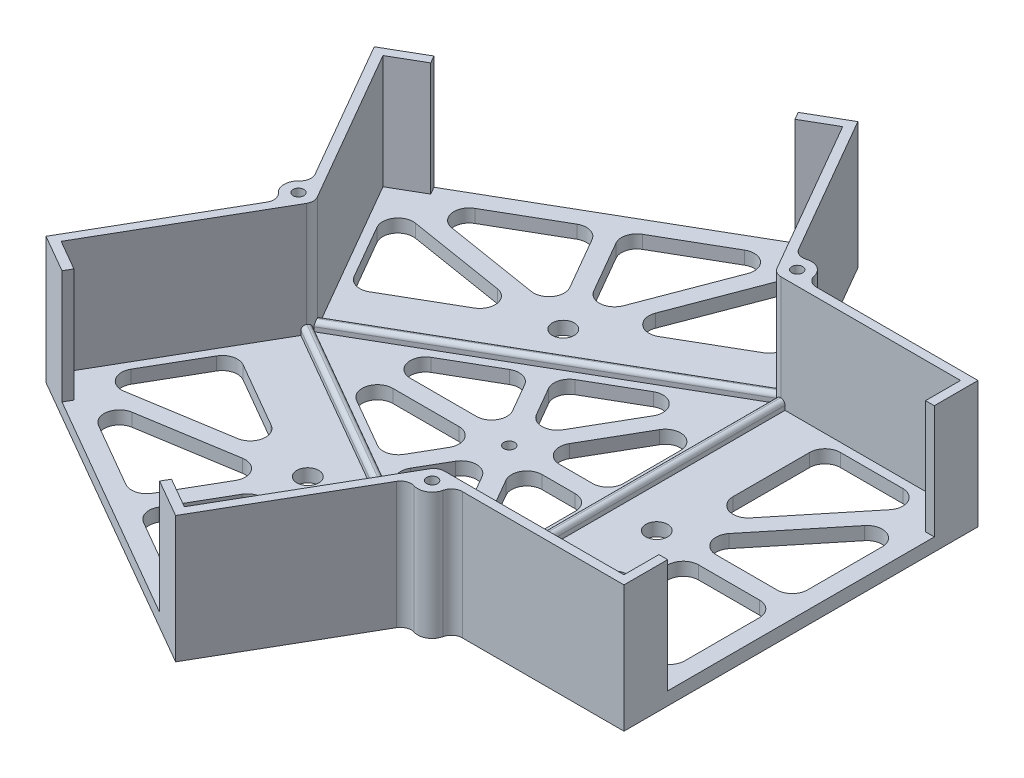
SolidWorks part; units mm, degrees
ref_plane "Front Plane" through (0, 0, 0) normal (0, 0, 1) x (1, 0, 0)
ref_plane "Top Plane" through (0, 0, 0) normal (0, 1, 0) x (1, 0, 0)
ref_plane "Right Plane" through (0, 0, 0) normal (1, 0, 0) x (0, 0, -1)
sketch "Sketch1" plane through (0, 0, 0) normal (0, 1, 0) x (1, 0, 0)
  line L0 (-19.4617, -68.9294) -> (-33.415, -32.2478)
  line L1 (-15.5479, 2.6989) -> (-16.7979, 0.5338)
  line L2 (50.5658, -38.8837) -> (50.5658, 42.1163)
  line L3 (-49.5423, -56.1811) -> (-14.4683, -76.4311)
  line L4 (-66.1729, -6.1649) -> (-66.1729, -0.3837)
  line L5 (-49.5423, -56.1811) -> (-84.6163, -35.9311)
  line L6 (-84.6163, -35.9311) -> (-68.1729, -7.4503)
  line L7 (-84.6163, 39.1637) -> (-68.1729, 10.683)
  line L8 (-14.4683, 79.6637) -> (1.9751, 51.183)
  line L9 (-66.1729, 1.6163) -> (-18.4823, 1.6163)
  line L10 (-84.6163, 39.1637) -> (-14.4683, 79.6637)
  line L11 (50.5658, 42.1163) -> (17.679, 42.1163)
  line L12 (50.5658, -38.8837) -> (17.679, -38.8837)
  line L13 (-14.4683, -76.4311) -> (1.9751, -47.9503)
  line L14 (2.0883, 48.8082) -> (7.095, 45.9176)
  line L15 (-33.7744, -24.8702) -> (-66.1729, -6.1649)
  line L16 (8.8271, 44.9176) -> (-15.0182, 3.6163)
  line L17 (-68.1729, -7.4503) -> (-68.1729, 10.683)
  line L18 (-38.91, -26.5239) -> (-65.6522, -11.0843)
  line L19 (19.5658, -4.0044) -> (19.5658, -34.8837)
  line L20 (1.9751, -47.9503) -> (17.679, -38.8837)
  line L21 (1.9751, 51.183) -> (17.679, 42.1163)
  line L22 (15.5658, -0.3837) -> (15.5658, -37.7943)
  line L23 (-29.1746, 35.3773) -> (-2.4324, 50.817)
  line L24 (10.5591, 43.9176) -> (15.5658, 41.027)
  line L25 (15.5658, -37.7943) -> (10.5591, -40.6849)
  line L26 (-30.3103, 30.1029) -> (2.0883, 48.8082)
  line L27 (8.8271, -41.6849) -> (-15.0182, -0.3837)
  line L28 (-17.3276, 3.6163) -> (-31.7524, 28.6007)
  line L29 (-17.4229, 1.6163) -> (-14.9229, 1.6163)
  line L30 (-17.3276, -0.3837) -> (-31.7524, -25.368)
  line L31 (-15.5479, 0.5338) -> (-16.7979, 2.6989)
  line L32 (-65.6522, 14.317) -> (-38.91, 29.7566)
  line L33 (19.5658, 38.1163) -> (19.5658, 7.2371)
  line L34 (-2.4324, -47.5843) -> (-29.1746, -32.1447)
  line L35 (-66.1729, 9.3975) -> (-33.7744, 28.1029)
  line L36 (15.5658, 41.027) -> (15.5658, 3.6163)
  line L37 (2.0883, -45.5755) -> (-30.3103, -26.8702)
  line L38 (7.095, 45.9176) -> (-16.1729, 5.6163)
  line L39 (-66.1729, -0.3837) -> (-19.637, -0.3837)
  line L40 (10.5591, -40.6849) -> (-12.7088, -0.3837)
  line L41 (10.5591, 43.9176) -> (-12.7088, 3.6163)
  line L42 (-66.1729, 3.6163) -> (-19.637, 3.6163)
  line L43 (7.095, -42.6849) -> (-16.1729, -2.3837)
  line L44 (-13.8635, 1.6163) -> (14.9859, 1.6163)
  line L45 (-16.1729, 5.6163) -> (-30.3103, 30.1029)
  line L46 (-12.7088, 3.6163) -> (15.5658, 3.6163)
  line L47 (-19.637, -0.3837) -> (-33.7744, -24.8702)
  line L48 (-19.637, 3.6163) -> (-33.7744, 28.1029)
  line L49 (-12.7088, -0.3837) -> (15.5658, -0.3837)
  line L50 (-16.1729, -2.3837) -> (-30.3103, -26.8702)
  line L51 (-53.8858, -0.3837) -> (-28.1992, -15.2138)
  line L52 (4.4155, -30.0439) -> (4.4155, -0.3837)
  line L53 (0.9514, 35.2766) -> (-24.7351, 20.4465)
  line L54 (4.4155, 3.6163) -> (4.4155, 33.2766)
  line L55 (-78.2327, 36.1069) -> (-65.6522, 14.317)
  line L56 (-75.6229, 39.7373) -> (-49.2744, 54.9496)
  line L57 (-15.0128, 72.6069) -> (-2.4324, 50.817)
  line L58 (-15.0128, -69.3743) -> (-2.4324, -47.5843)
  line L59 (-45.8103, -53.717) -> (-19.4617, -68.9294)
  line L60 (-49.2744, -51.717) -> (-75.6229, -36.5046)
  line L61 (-78.2327, -32.8743) -> (-65.6522, -11.0843)
  line L62 (44.7266, 38.1163) -> (19.5658, 38.1163)
  line L63 (-28.1992, 18.4465) -> (-53.8858, 3.6163)
  line L64 (46.5658, -30.8084) -> (46.5658, -0.3837)
  line L65 (44.7266, -34.8837) -> (19.5658, -34.8837)
  line L66 (-24.7351, -17.2138) -> (0.9514, -32.0439)
  line L67 (-38.91, -26.5239) -> (-78.2327, -32.8743)
  line L68 (-15.0128, -69.3743) -> (-29.1746, -32.1447)
  line L69 (-66.1729, 3.6163) -> (-66.1729, 9.3975)
  line L70 (44.7266, 38.1163) -> (19.5658, 7.2371)
  line L71 (7.095, -42.6849) -> (2.0883, -45.5755)
  line L72 (-29.1746, 35.3773) -> (-15.0128, 72.6069)
  line L73 (-78.2327, 36.1069) -> (-38.91, 29.7566)
  line L74 (-36.8791, -30.2478) -> (-75.6229, -36.5046)
  line L75 (46.5658, 34.041) -> (21.7753, 3.6163)
  line L76 (21.7753, -0.3837) -> (46.5658, -30.8084)
  line L77 (-33.415, 35.4804) -> (-19.4617, 72.162)
  line L78 (-75.6229, 39.7373) -> (-36.8791, 33.4804)
  line L79 (46.5658, 3.6163) -> (46.5658, 34.041)
  line L80 (19.5658, -4.0044) -> (44.7266, -34.8837)
  line L81 (-45.8103, 56.9496) -> (-19.4617, 72.162)
  line L82 (46.5658, 3.6163) -> (21.7753, 3.6163)
  line L83 (-33.415, 35.4804) -> (-45.8103, 56.9496)
  line L84 (-45.8103, -53.717) -> (-33.415, -32.2478)
  line L85 (46.5658, -0.3837) -> (21.7753, -0.3837)
  line L86 (-36.8791, 33.4804) -> (-49.2744, 54.9496)
  line L87 (-49.2744, -51.717) -> (-36.8791, -30.2478)
  circle A0 centre (-33.0423, -27.6023) radius 2.5
  circle A1 centre (-33.0423, 30.8349) radius 2.5
  circle A2 centre (17.5658, 1.6163) radius 2.5
  circle A3 centre (-16.1729, 1.6163) radius 1.25
  point P6 (50.5658, 1.6163)
  point P11 (-49.5423, -56.1811)
  point P14 (-49.5423, 59.4137)
  point P15 (-49.5423, -56.1811)
  point P26 (-68.1729, 1.6163)
  point P32 (9.8271, -43.417)
  point P36 (9.8271, 46.6496)
  point P64 (-16.1729, 1.6163)
  point P94 (-16.1729, 1.6163)
extrude "Boss-Extrude1" add sketch "Sketch1" along normal blind 3 contours L21 L8 L10 L7 L17 L6 L5 L3 L13 L20 L12 L2 L11 A3 A2 A1 A0 L87 L60 L74 L86 L78 | L69 L42 L63 L48 L35 | L53 L38 L14 L26 L45 | L54 L46 L36 L24 L41 | L52 L40 L25 L22 L49 | L71 L43 L66 L50 L37 | L51 L39 L4 L15 L47 region at (34.1224, 0, 36.8187) region at (-47.1024, 0, 10.9831) region at (-11.6196, 0, -34.7018) region at (10.2032, 0, 18.8697) region at (10.2032, 0, -22.1024) region at (-47.1024, 0, -14.2157) region at (-11.6196, 0, 31.4691)
sketch "Sketch2" plane through (0, 3, 0) normal (0, 1, 0) x (1, 0, 0)
  line L1 (-14.4683, 79.6637) -> (1.9751, 51.183)
  line L2 (1.9751, 51.183) -> (17.679, 42.1163)
  line L3 (17.679, 42.1163) -> (50.5658, 42.1163)
  line L5 (50.5658, -38.8837) -> (17.679, -38.8837)
  line L6 (17.679, -38.8837) -> (1.9751, -47.9503)
  line L7 (1.9751, -47.9503) -> (-14.4683, -76.4311)
  line L9 (-84.6163, -35.9311) -> (-68.1729, -7.4503)
  line L10 (-68.1729, -7.4503) -> (-68.1729, 10.683)
  line L11 (-68.1729, 10.683) -> (-84.6163, 39.1637)
  line L12 (-60.6289, 1.6163) -> (-62.9383, 1.6163)
  line L13 (6.055, 40.1163) -> (7.2097, 42.1163)
  line L14 (9.8271, -43.417) -> (7.316, -39.0678)
  line L15 (-60.6289, 1.6163) -> (-81.8843, 38.4317)
  line L17 (-15.2003, 76.9317) -> (6.055, 40.1163)
  line L18 (6.055, 40.1163) -> (48.5658, 40.1163)
  line L20 (48.5658, -36.8837) -> (6.055, -36.8837)
  line L21 (6.055, -36.8837) -> (-15.2003, -73.699)
  line L23 (-81.8843, -35.199) -> (-60.6289, 1.6163)
  line L24 (-15.2003, -73.699) -> (-81.8843, -35.199) construction
  line L25 (-14.4683, -76.4311) -> (-84.6163, -35.9311) construction
  line L26 (-81.8843, -35.199) -> (-74.9561, -39.199)
  line L27 (-74.9561, -39.199) -> (-75.9561, -40.9311)
  line L28 (-14.4683, -76.4311) -> (-84.6163, -35.9311) construction
  line L29 (-75.9561, -40.9311) -> (-84.6163, -35.9311)
  line L30 (-15.2003, -73.699) -> (-22.1285, -69.699)
  line L31 (-22.1285, -69.699) -> (-23.1285, -71.4311)
  line L32 (-23.1285, -71.4311) -> (-14.4683, -76.4311)
  line L33 (48.5658, 40.1163) -> (48.5658, 32.1163)
  line L34 (48.5658, 40.1163) -> (48.5658, -36.8837) construction
  line L35 (50.5658, 42.1163) -> (50.5658, -38.8837) construction
  line L36 (-84.6163, 39.1637) -> (-14.4683, 79.6637) construction
  line L37 (-81.8843, 38.4317) -> (-15.2003, 76.9317) construction
  line L38 (48.5658, 32.1163) -> (50.5658, 32.1163)
  line L39 (50.5658, -38.8837) -> (50.5658, 42.1163) construction
  line L40 (50.5658, 32.1163) -> (50.5658, 42.1163)
  line L41 (48.5658, -36.8837) -> (48.5658, -28.8837)
  line L42 (48.5658, -28.8837) -> (50.5658, -28.8837)
  line L43 (50.5658, -28.8837) -> (50.5658, -38.8837)
  line L44 (-15.2003, 76.9317) -> (-22.1285, 72.9317)
  line L45 (-22.1285, 72.9317) -> (-23.1285, 74.6637)
  line L46 (-84.6163, 39.1637) -> (-14.4683, 79.6637) construction
  line L47 (-23.1285, 74.6637) -> (-14.4683, 79.6637)
  line L48 (-81.8843, 38.4317) -> (-74.9561, 42.4317)
  line L49 (-74.9561, 42.4317) -> (-75.9561, 44.1637)
  line L50 (-75.9561, 44.1637) -> (-84.6163, 39.1637)
  line L51 (-84.6163, -35.9311) -> (-62.9383, 1.6163) construction
  line L52 (-63.1509, 1.6163) -> (-68.1729, 1.6163)
  line L53 (-62.9383, 1.6163) -> (-84.6163, 39.1637) construction
  line L54 (7.2097, -38.8837) -> (-14.4683, -76.4311) construction
  line L55 (7.2097, -38.8837) -> (6.055, -36.8837)
  line L56 (50.5658, -38.8837) -> (7.2097, -38.8837) construction
  line L57 (7.2097, 42.1163) -> (50.5658, 42.1163) construction
  line L58 (7.316, 42.3005) -> (9.8271, 46.6496)
  line L59 (-14.4683, 79.6637) -> (7.2097, 42.1163) construction
  circle A3 centre (-64.4009, 1.6163) radius 1.25
  circle A4 centre (7.941, -40.1503) radius 1.25
  circle A5 centre (7.941, 43.383) radius 1.25
  dimension "D1" = 2
extrude "Boss-Extrude2" add sketch "Sketch2" along normal blind 26 contours L49 L50 L11 L9 L29 L27 L26 L23 L15 L48 | A3 L10 L9 | A3 L11 L10 | L47 L45 L44 L17 L18 L33 L38 L40 L3 L1 | A5 L3 L2 | A5 L2 L1 | L43 L42 L41 L20 L21 L30 L31 L32 L7 L5 | A4 L7 L6 | A4 L6 L5 region at (-7.0061, 3, -64.9848) region at (34.1224, 3, 38.0067) region at (-75.629, 3, 22.1328)
sketch "Sketch3" plane through (0, 29, 0) normal (0, 1, 0) x (1, 0, 0)
  line L0 (-84.6163, 39.1637) -> (-64.8095, 4.8573)
  line L1 (-84.6163, -35.9311) -> (-64.8095, -1.6247)
  line L2 (-14.4683, -76.4311) -> (5.3385, -42.1247)
  line L3 (50.5658, -38.8837) -> (10.9521, -38.8837)
  line L4 (50.5658, 42.1163) -> (10.9521, 42.1163)
  line L6 (-14.4683, 79.6637) -> (5.3385, 45.3573)
  line L7 (1.9751, 51.183) -> (17.679, 42.1163)
  line L8 (-68.1729, -7.4503) -> (-68.1729, 10.683)
  line L9 (17.679, -38.8837) -> (1.9751, -47.9503)
  circle A0 centre (-64.4009, 1.6163) radius 3.2667
  circle A1 centre (7.941, 43.383) radius 3.2667
  circle A2 centre (7.941, -40.1503) radius 3.2667
  line M4 (-68.1729, 10.683) -> (-68.1729, -7.4503)
extrude "Cut-Extrude1" cut sketch "Sketch3" against normal through all contours A0 L0 L1 M4 | A2 L2 L9 L3 | A1 L4 L7 L6 region at (-66.6509, 29, -7.6779) region at (3.8139, 29, 45.1282) region at (14.3156, 29, -42.2977)
fillet "Fillet1" radius 2.5 9 edges at (6.055, 16, 36.8837) (-60.6289, 16, -1.6163) (6.055, 16, -40.1163) (5.3385, 14.5, -45.3573) (10.9521, 14.5, -42.1163) (5.3385, 14.5, 42.1247) (10.9521, 14.5, 38.8837) (-64.8095, 14.5, 1.6247) (-64.8095, 14.5, -4.8573)
fillet "Fillet2" radius 3.5 54 edges at (-33.415, 1.5, -35.4804) (-2.4324, 1.5, -50.817) (-19.4617, 1.5, -72.162) (-15.0128, 1.5, -72.6069) (-29.1746, 1.5, -35.3773) (-75.6229, 1.5, -39.7373) (-78.2327, 1.5, -36.1069) (-65.6522, 1.5, -14.317) (-38.91, 1.5, -29.7566) (-36.8791, 1.5, -33.4804) (-49.2744, 1.5, -54.9496) (-45.8103, 1.5, -56.9496) (46.5658, 1.5, -34.041) (44.7266, 1.5, -38.1163) (19.5658, 1.5, -38.1163) (46.5658, 1.5, 30.8084) (44.7266, 1.5, 34.8837) (19.5658, 1.5, 34.8837) (46.5658, 1.5, 0.3837) (46.5658, 1.5, -3.6163) (19.5658, 1.5, -7.2371) (21.7753, 1.5, -3.6163) (19.5658, 1.5, 4.0044) (21.7753, 1.5, 0.3837) (0.9514, 1.5, 32.0439) (4.4155, 1.5, 30.0439) (4.4155, 1.5, 0.3837) (4.4155, 1.5, -3.6163) (4.4155, 1.5, -33.2766) (0.9514, 1.5, -35.2766) (-24.7351, 1.5, -20.4465) (-12.7088, 1.5, 0.3837) (-16.1729, 1.5, 2.3837) (-16.1729, 1.5, -5.6163) (-12.7088, 1.5, -3.6163) (-28.1992, 1.5, -18.4465) (-19.637, 1.5, -3.6163) (-19.637, 1.5, 0.3837) (-28.1992, 1.5, 15.2138) (-24.7351, 1.5, 17.2138) (-53.8858, 1.5, -3.6163) (-53.8858, 1.5, 0.3837) (-2.4324, 1.5, 47.5843) (-19.4617, 1.5, 68.9294) (-15.0128, 1.5, 69.3743) (-29.1746, 1.5, 32.1447) (-33.415, 1.5, 32.2478) (-36.8791, 1.5, 30.2478) (-38.91, 1.5, 26.5239) (-45.8103, 1.5, 53.717) (-49.2744, 1.5, 51.717) (-65.6522, 1.5, 11.0843) (-75.6229, 1.5, 36.5046) (-78.2327, 1.5, 32.8743)
sketch "Sketch4" plane through (0, 3, 0) normal (0, 1, 0) x (1, 0, 0)
  line L0 (-57.3499, 1.6163) -> (4.4155, 37.2766)
  line L1 (-61.3499, 1.6163) -> (6.4155, 40.7407)
  line L2 (4.4155, -34.0439) -> (4.4155, 37.2766)
  line L3 (-57.3499, 1.6163) -> (4.4155, -34.0439)
  line L4 (6.4155, -37.508) -> (6.4155, 40.7407)
  line L5 (-61.3499, 1.6163) -> (6.4155, -37.508)
  line L6 (-65.3499, 1.6163) -> (8.4155, 44.2048)
  line L7 (8.4155, -40.9721) -> (8.4155, 44.2048)
  line L8 (-65.3499, 1.6163) -> (8.4155, -40.9721)
  circle A0 centre (-63.5157, 1.6163) radius 2.5
  circle A1 centre (7.4984, 42.6163) radius 2.5
  circle A2 centre (7.4984, -39.3837) radius 2.5
  dimension "D1" = 2
  dimension "D2" = 2
extrude "Boss-Extrude3" add sketch "Sketch4" along normal blind 2 contours A1 L6 A0 L1 | A2 L5 A0 L8 | A2 L7 A1 L4 region at (-27.967, 3, -22.0443) region at (-27.967, 3, 18.8116) region at (7.4152, 3, -1.6163)
fillet "Fillet3" radius 1 6 edges at (-27.4672, 5, 17.9459) (-28.4672, 5, 19.6779) (8.4155, 5, -1.6163) (6.4155, 5, -1.6163) (-28.4672, 5, -22.9106) (-27.4672, 5, -21.1785)
